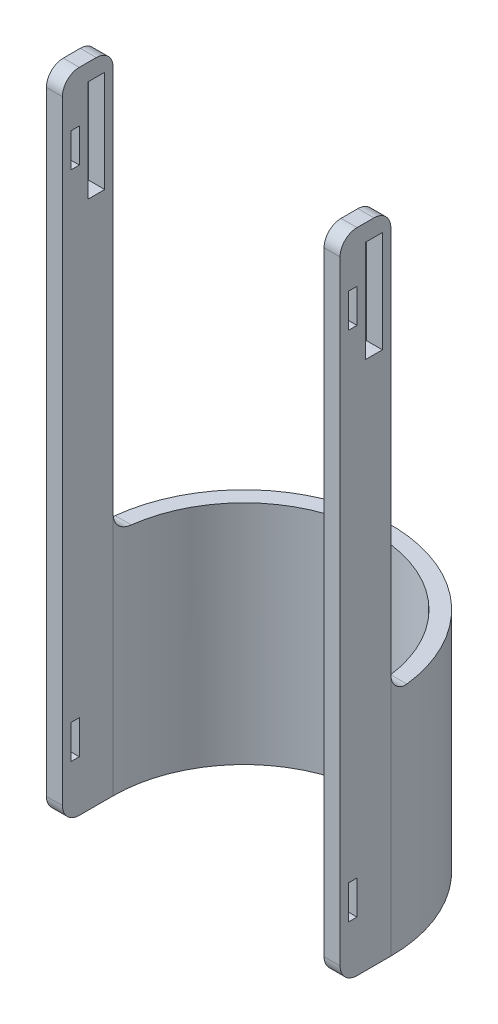
SolidWorks part; units mm, degrees
other "Markup1"
sketch "Sketch11" plane through (-75, 302.2666, -81.3292) normal (-0.1024, 0.768, -0.6322) x (-0.9876, -0.0025, 0.157)
material "PE High Density"
ref_plane "Front Plane" through (0, 0, 0) normal (0, 0, 1) x (1, 0, 0)
ref_plane "Top Plane" through (0, 0, 0) normal (0, 1, 0) x (1, 0, 0)
ref_plane "Right Plane" through (0, 0, 0) normal (1, 0, 0) x (0, 0, -1)
sketch "Sketch1" plane through (0, 0, 0) normal (0, 1, 0) x (1, 0, 0)
  line L0 (-86.724, 0) -> (86.724, 0) construction
  line L1 (-77.2727, 0) -> (-86.724, 0)
  line L2 (86.724, 0) -> (77.2727, 0)
  arc A0 (86.724, 0) -> (-86.724, 0) centre (0, 0) ccw
  arc A1 (77.2727, 0) -> (-77.2727, 0) centre (0, 0) ccw
  dimension "D1" = 77.2727
  dimension "D2" = 86.724
extrude "Boss-Extrude1" add sketch "Sketch1" along normal blind 133.8944
sketch "Sketch2" plane through (0, 0, 0) normal (0, 0, 1) x (1, 0, 0)
  line L1 (77.2727, 133.8944) -> (86.724, 133.8944)
  line L2 (77.2727, 133.8944) -> (77.2727, 0)
  line L3 (77.2727, 0) -> (86.724, 0)
  line L4 (86.724, 133.8944) -> (86.724, 0)
  line L5 (-86.724, 133.8944) -> (-77.2727, 133.8944)
  line L6 (-86.724, 133.8944) -> (-86.724, 0)
  line L7 (-86.724, 0) -> (-77.2727, 0)
  line L8 (-77.2727, 133.8944) -> (-77.2727, 0)
extrude "Boss-Extrude2" add sketch "Sketch2" along normal blind 30
sketch "Sketch3" plane through (0, 133.8944, 0) normal (0, 1, 0) x (1, 0, 0)
  line L1 (-77.2727, -30) -> (-86.724, -30)
  line L2 (-77.2727, -30) -> (-77.2727, 0)
  line L3 (-77.2727, 0) -> (-86.724, 0)
  line L4 (-86.724, -30) -> (-86.724, 0)
  line L5 (86.724, -30) -> (77.2727, -30)
  line L6 (86.724, -30) -> (86.724, 0)
  line L7 (86.724, 0) -> (77.2727, 0)
  line L8 (77.2727, -30) -> (77.2727, 0)
extrude "Boss-Extrude3" add sketch "Sketch3" along normal blind 248.75
sketch "Sketch5" plane through (-86.724, 0, 0) normal (-1, 0, 0) x (0, 0, 1)
  line L0 (0, 382.6444) -> (30, 382.6444) construction
  line L1 (5, 372.6444) -> (15, 372.6444)
  line L2 (5, 372.6444) -> (5, 312.6444)
  line L3 (5, 312.6444) -> (15, 312.6444)
  line L4 (15, 372.6444) -> (15, 312.6444)
  line L5 (0, 382.6444) -> (0, 133.8944) construction
  dimension "D1" = 60
  dimension "D2" = 10
  dimension "D3" = 10
  dimension "D4" = 5
extrude "Cut-Extrude1" cut sketch "Sketch5" against normal blind 240
sketch "Sketch6" plane through (-86.724, 0, 0) normal (-1, 0, 0) x (0, 0, 1)
  line L0 (17.5605, 360) -> (17.5605, 300) construction
  line L1 (20, 352.6444) -> (25, 352.6444)
  line L2 (20, 352.6444) -> (20, 332.6444)
  line L3 (20, 332.6444) -> (25, 332.6444)
  line L4 (25, 352.6444) -> (25, 332.6444)
  line L5 (15, 372.6444) -> (5, 372.6444) construction
  line L7 (15, 312.6444) -> (15, 372.6444) construction
  dimension "D1" = 20
  dimension "D2" = 5
  dimension "D3" = 20
  dimension "D4" = 5
extrude "Cut-Extrude2" cut sketch "Sketch6" against normal through all
fillet "Fillet1" radius 10 4 edges at (81.9984, 382.6444, 30) (-81.9984, 382.6444, 30) (-81.9984, 382.6444, 0) (81.9984, 382.6444, 0)
fillet "Fillet2" radius 10 2 edges at (81.9984, 0, 30) (-81.9984, 0, 30)
fillet "Fillet3" radius 10 2 edges at (81.9984, 133.8944, 0) (-81.9984, 133.8944, 0)
sketch "Sketch8" plane through (-86.724, 0, 0) normal (-1, 0, 0) x (0, 0, 1)
  line L1 (20, 50) -> (25, 50)
  line L2 (20, 50) -> (20, 30)
  line L3 (20, 30) -> (25, 30)
  line L4 (25, 50) -> (25, 30)
  line L5 (20, 0) -> (0, 0) construction
  line L6 (30, 372.6444) -> (30, 10) construction
  dimension "D1" = 20
  dimension "D2" = 5
  dimension "D3" = 30
  dimension "D4" = 5
extrude "Cut-Extrude3" cut sketch "Sketch8" against normal through all
ref_plane "Plane1" through (0, 68.8944, 0) normal (0, 1, 0) x (1, 0, 0)
sketch "Sketch9" plane through (0, 68.8944, 0) normal (0, 1, 0) x (1, 0, 0)
  line L0 (-26.7992, 82.4794) -> (-26.7992, 92.4794)
  line L1 (-26.7992, 92.4794) -> (26.7992, 92.4794)
  line L2 (26.7992, 92.4794) -> (26.7992, 82.4794)
  line L3 (-86.724, 0) -> (86.724, 0)
  line L4 (0, 0) -> (-26.7992, 82.4794) construction
  line L5 (0, 0) -> (26.7992, 82.4794) construction
  arc A0 (86.1455, 10) -> (-86.1455, 10) centre (0, 0) ccw construction
  arc A1 (86.724, 0) -> (-26.7992, 82.4794) centre (0, 0) ccw
  point P13 (0, 0)
  dimension "D1" = 72
  dimension "D2" = 72
  dimension "D3" = 10
  dimension "D4" = 10
extrude "Boss-Extrude4" add sketch "Sketch9" along normal mid plane 61.7166 contours A1 L2 L1 L0 region at (0, 68.8944, -88.7903)
fillet "Fillet4" radius 5 4 edges at (0, 38.0361, -92.4794) (26.7992, 68.8944, -92.4794) (-26.7992, 68.8944, -92.4794) (0, 99.7527, -92.4794)
sketch "Sketch10" plane through (0, 0, -92.4794) normal (0, 0, -1) x (-1, 0, 0)
  line L0 (21.7992, 94.7527) -> (-21.7992, 94.7527) construction
  line L1 (-21.7992, 94.7527) -> (-21.7992, 43.0361) construction
  line L2 (21.7992, 43.0361) -> (21.7992, 94.7527) construction
  line L3 (21.7992, 94.7527) -> (-21.7992, 94.7527) construction
  line L4 (-21.7992, 43.0361) -> (21.7992, 43.0361) construction
  line L5 (-21.7992, 43.0361) -> (21.7992, 43.0361) construction
  circle A0 centre (-16.7992, 89.7527) radius 1.0922
  circle A1 centre (16.7992, 89.7527) radius 1.0922
  circle A2 centre (-16.7992, 48.0361) radius 1.0922
  circle A3 centre (16.7992, 48.0361) radius 1.0922
  dimension "D1" = 2.1844
  dimension "D2" = 2.1844
  dimension "D3" = 2.1844
  dimension "D4" = 2.1844
  dimension "D5" = 5
  dimension "D7" = 5
  dimension "D8" = 5
  dimension "D9" = 5
  dimension "D10" = 5
  dimension "D11" = 5
  dimension "D12" = 5
  dimension "D6" = 5
extrude "Cut-Extrude4" cut sketch "Sketch10" against normal blind 5
cosmetic thread "Cosmetic Thread6" parameters "D2"=3.1844
cosmetic thread "Cosmetic Thread7" parameters "D2"=3.1844
cosmetic thread "Cosmetic Thread8" parameters "D2"=3.1844
cosmetic thread "Cosmetic Thread9" parameters "D2"=3.1844
equation "\"userHeight\"= 1700mm'Users height"
equation "\"shell_length\"=133.89441469"
equation "\"D1@Boss-Extrude1\"=\"shell_length\""
equation "\"partial_sidebar_length\"=248.75000000"
equation "\"shell_outer_radius\" = 86.724"
equation "\"D2@Sketch1\"=\"shell_outer_radius\""
equation "\"shell_inner_radius\"= \"userHeight\" / 22'Shell inner radius"
equation "\"D1@Sketch1\"=\"shell_inner_radius\""
equation "\"fin_platform_height\"= 51.7166 + 10"
equation "\"D1@Boss-Extrude4\"=\"fin_platform_height\""
equation "\"D1@Boss-Extrude3\"=\"partial_sidebar_length\""
equation "\"fin_platform_width\" = 43.598"
equation "\"fin_thickness\"=3.00000000"
